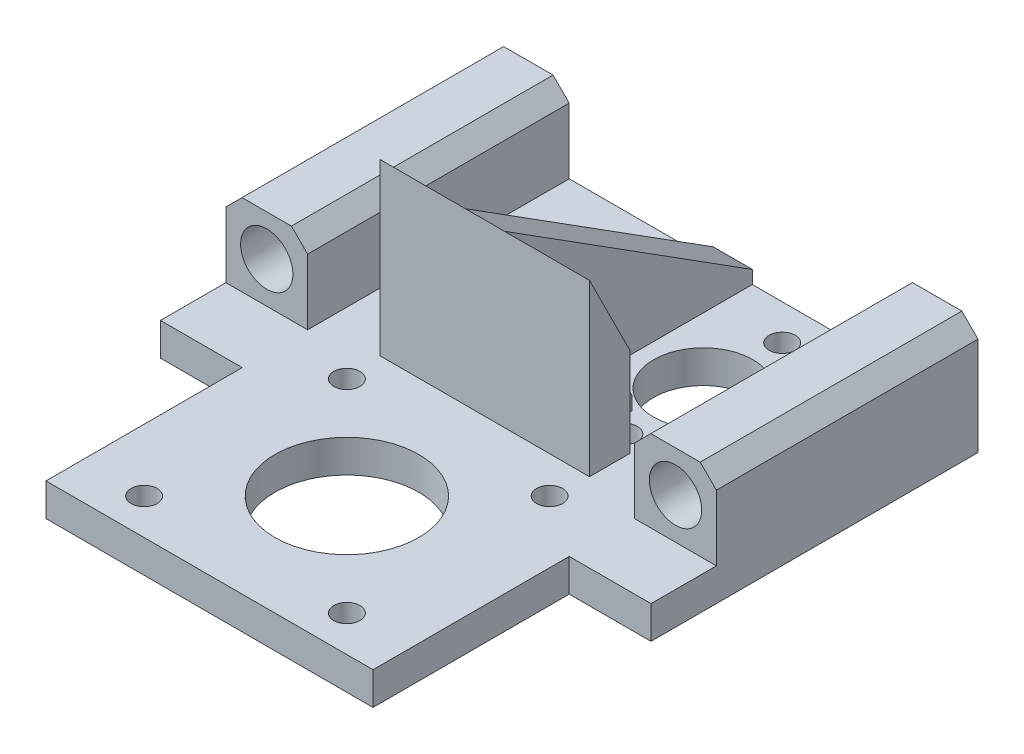
SolidWorks part; units mm, degrees
ref_plane "Front Plane" through (0, 0, 0) normal (0, 0, 1) x (1, 0, 0)
ref_plane "Top Plane" through (0, 0, 0) normal (0, 1, 0) x (1, 0, 0)
ref_plane "Right Plane" through (0, 0, 0) normal (1, 0, 0) x (0, 0, -1)
sketch "Sketch1" plane through (0, 0, 0) normal (0, 1, 0) x (1, 0, 0)
  line L0 (0, 32.5) -> (75, 32.5) construction
  line L1 (0, 0) -> (75, 0)
  line L2 (0, 0) -> (0, 50)
  line L3 (0, 50) -> (75, 50)
  line L4 (75, 0) -> (75, 50)
  line L5 (37.5, 50) -> (37.5, 0) construction
  line L6 (37.5, 32.5) -> (24.5, 32.5) construction
  line L7 (37.5, 32.5) -> (50.5, 32.5) construction
  circle A0 centre (24.5, 32.5) radius 5.1
  circle A1 centre (50.5, 32.5) radius 7.6
  point P13 (48.5535, 18.2187)
  point P14 (0, 0)
  point P15 (37.5, 32.5)
  point P16 (75, 35.4006)
  point P18 (0, 35.3582)
  dimension "D2" = 10.2
  dimension "D6" = 15.2
  dimension "D1" = 26
  dimension "D3" = 75
  dimension "D4" = 50
  dimension "D5" = 17.5
extrude "Boss-Extrude1" add sketch "Sketch1" along normal blind 5
sketch "Sketch2" plane through (0, 5, 0) normal (0, 1, 0) x (1, 0, 0)
  line L4 (0, 50) -> (12.5, 50)
  line L5 (0, 50) -> (0, 10)
  line L6 (0, 10) -> (12.5, 10)
  line L7 (12.5, 50) -> (12.5, 10)
  line L8 (75, 50) -> (62.5, 50)
  line L9 (75, 50) -> (75, 10)
  line L10 (75, 10) -> (62.5, 10)
  line L11 (62.5, 50) -> (62.5, 10)
  dimension "D1" = 40
  dimension "D3" = 12.5
extrude "Boss-Extrude2" add sketch "Sketch2" along normal blind 12.5
sketch "Sketch3" plane through (0, 0, -50) normal (0, 0, -1) x (-1, 0, 0)
  line L0 (-37.5, 0) -> (-37.5, 50000) construction
  line L1 (-75, 0) -> (0, 0) construction
  line L2 (-62.5, 5) -> (-12.5, 5) construction
  line L3 (-72.5251, 17.5) -> (-75, 17.5)
  line L4 (-75, 17.5) -> (-62.5, 17.5) construction
  line L5 (-75, 17.5) -> (-75, 15.0251)
  line L6 (-75, 17.5) -> (-75, 0) construction
  line L7 (-75, 15.0251) -> (-72.5251, 17.5)
  line L8 (-62.5, 17.5) -> (-64.9749, 17.5)
  line L9 (-64.9749, 17.5) -> (-62.5, 15.0251)
  line L10 (-62.5, 17.5) -> (-62.5, 5) construction
  line L11 (-62.5, 15.0251) -> (-62.5, 17.5)
  line L12 (-68.75, 17.5) -> (-68.75, 0) construction
  line L13 (-62.5, 11.25) -> (-75, 11.25) construction
  line L14 (-12.5, 11.25) -> (0, 11.25) construction
  line L15 (-6.25, 17.5) -> (-6.25, 0) construction
  line L16 (-12.5, 15.0251) -> (-12.5, 17.5)
  line L17 (-10.0251, 17.5) -> (-12.5, 15.0251)
  line L18 (-12.5, 17.5) -> (-10.0251, 17.5)
  line L19 (0, 15.0251) -> (-2.4749, 17.5)
  line L20 (0, 17.5) -> (0, 15.0251)
  line L21 (-2.4749, 17.5) -> (0, 17.5)
  circle A0 centre (-68.75, 11.25) radius 4
  circle A1 centre (-6.25, 11.25) radius 4
  point P4 (-37.5, 0)
  point P7 (-37.5, 5)
  point P28 (-68.75, 11.25)
  dimension "D1" = 8
  dimension "D2" = 3.5
extrude "Cut-Extrude1" cut sketch "Sketch3" against normal through all
sketch "Sketch4" plane through (0, 5, 0) normal (0, 1, 0) x (1, 0, 0)
  line L0 (0, 0) -> (75, 0) construction
  line L1 (62.5, 0) -> (12.5, 0)
  line L2 (62.5, 0) -> (62.5, -30)
  line L3 (62.5, -30) -> (12.5, -30)
  line L4 (12.5, 0) -> (12.5, -30)
  line L5 (37.5, 50) -> (37.5, 0) construction
  line L6 (62.5, 50) -> (12.5, 50) construction
  point P10 (37.5, 0)
  dimension "D1" = 50
  dimension "D2" = 30
extrude "Boss-Extrude3" add sketch "Sketch4" against normal up to surface (5 mm away) up to face at (24.5, 0, -27.4)
sketch "Sketch5" plane through (0, 5, 0) normal (0, 1, 0) x (1, 0, 0)
  line L0 (37.5, -30) -> (37.5, 50) construction
  line L1 (12.5, -30) -> (62.5, -30) construction
  line L2 (62.5, 50) -> (12.5, 50) construction
  line L3 (58.5, -9) -> (16.5, -9) construction
  circle A0 centre (22, -24.5) radius 2
  circle A1 centre (22, 6.5) radius 2
  circle A2 centre (53, 6.5) radius 2
  circle A3 centre (53, -24.5) radius 2
  circle A4 centre (37.5, -9) radius 11
  point P8 (37.5, -9)
  point P19 (37.5, -9)
  dimension "D5" = 4
  dimension "D6" = 22
  dimension "D1" = 42
  dimension "D2" = 21
  dimension "D3" = 15.5
  dimension "D4" = 15.5
extrude "Cut-Extrude2" cut sketch "Sketch5" against normal through all
sketch "Sketch6" plane through (0, 5, 0) normal (0, 1, 0) x (1, 0, 0)
  line L0 (37.5, -30) -> (37.5, 12.1) construction
  line L1 (12.5, -30) -> (62.5, -30) construction
  line L3 (53.5, 12.1) -> (21.5, 12.1)
  line L4 (53.5, 12.1) -> (53.5, 24.1)
  line L5 (53.5, 24.1) -> (21.5, 24.1)
  line L6 (21.5, 12.1) -> (21.5, 24.1)
  point P8 (18.8582, 24.1)
  point P9 (37.5, 12.1)
  dimension "D1" = 42.1
  dimension "D2" = 12
  dimension "D3" = 32
extrude "Boss-Extrude4" add sketch "Sketch6" along normal blind 2
sketch "Sketch8" plane through (53.5, 0, 0) normal (1, 0, 0) x (0, 0, -1)
  line L0 (24.1, 7) -> (12.1, 7)
  line L1 (12.1, 7) -> (12.1, 31)
  line L2 (12.1, 31) -> (24.1, 7)
  dimension "D1" = 24
extrude "Boss-Extrude6" add sketch "Sketch8" against normal up to surface (32 mm away) up to face at (21.5, 6, -18.1)
sketch "Sketch9" plane through (0, 5, 0) normal (0, 1, 0) x (1, 0, 0)
  line L0 (62.5, 50) -> (12.5, 50) construction
  line L1 (40.5, 50) -> (34.5, 50)
  line L2 (40.5, 50) -> (40.5, 24.1)
  line L3 (40.5, 24.1) -> (34.5, 24.1)
  line L4 (34.5, 50) -> (34.5, 24.1)
  line L5 (53.5, 24.1) -> (21.5, 24.1) construction
  line L6 (37.5, 50) -> (37.5, -138.6407) construction
  point P10 (37.5, 50)
  point P11 (37.5, 50)
  dimension "D1" = 6
extrude "Boss-Extrude7" add sketch "Sketch9" along normal up to vertex (2 mm away) up to point (21.5, 7, -24.1)
sketch "Sketch10" plane through (34.5, 0, 0) normal (-1, 0, 0) x (0, 0, 1)
  line L0 (-50, 7) -> (-12.1, 31)
  line L1 (-12.1, 31) -> (-24.1, 7)
  line L2 (-24.1, 7) -> (-50, 7)
  line L3 (-12.1, 31) -> (-24.1, 7) construction
  point P3 (-13.7036, 27.4205)
  point P6 (-16.3524, 29.1452)
  point P9 (0, 0)
  point P10 (0, 0)
  point P11 (0, 0)
extrude "Boss-Extrude8" add sketch "Sketch10" against normal up to surface (6 mm away) up to face at (40.5, 6, -37.05)
sketch "Sketch11" plane through (0, 5, 5) normal (0, 1, 0) x (1, 0, 0)
  line L0 (50.5, 29.9) -> (50.5, 45.1) construction
  line L1 (24.5, 42.6) -> (24.5, 32.4) construction
  line L2 (29.6, 37.5) -> (19.4, 37.5) construction
  line L3 (29.6, 37.5) -> (19.4, 37.5) construction
  line L5 (50.5, 29.9) -> (50.5, 45.1) construction
  circle A0 centre (50.5, 37.5) radius 7.6 construction
  circle A1 centre (50.5, 25.43) radius 2
  circle A2 centre (50.5, 49.565) radius 2
  circle A3 centre (24.5, 37.5) radius 5.1 construction
  circle A6 centre (24.5, 45.5) radius 1.5
  circle A7 centre (16.5, 37.5) radius 1.5
  circle A8 centre (32.5, 37.5) radius 1.5
  circle A9 centre (24.5, 29.5) radius 1.5
  point P5 (24.5, 37.5)
  point P10 (50.5, 37.5)
  point P11 (24.5, 32.4)
  point P20 (24.5, 37.5)
  dimension "D3" = 4
  dimension "D6" = 3
  dimension "D1" = 12.065
  dimension "D2" = 12.07
  dimension "D4" = 8
  dimension "D5" = 8
extrude "Cut-Extrude3" cut sketch "Sketch11" against normal through all both and the other way through all
sketch "Sketch13" plane through (0, 5, 0) normal (0, 1, 0) x (1, 0, 0)
  line L1 (53.5, 24.1) -> (48, 24.1)
  line L2 (53.5, 24.1) -> (53.5, 22.4258)
  line L3 (53.5, 22.4258) -> (48, 22.4258)
  line L4 (48, 24.1) -> (48, 22.4258)
  circle A0 centre (50.5, 20.43) radius 3.7
  circle A1 centre (24.5, 24.5) radius 2.75
  line M35 (53.5, 24.1) -> (53.5, 12.1)
  dimension "D1" = 5.5
  dimension "D2" = 7.4
  dimension "D3" = 5.5
  dimension "D4" = 1.6742
extrude "Cut-Extrude4" cut sketch "Sketch13" along normal through all contours A0 L2 M35 | A1 | A0 | L1 L4 L3 L2 region at (53.7824, 5, -20.43)
equation "\"8mm hole\" = 8mm"
equation "\"22mm hole\"= 22mm"
equation "\"D6@Sketch5\"= \"22mm hole\""
equation "\"D1@Sketch3\"= \"8mm hole\""
